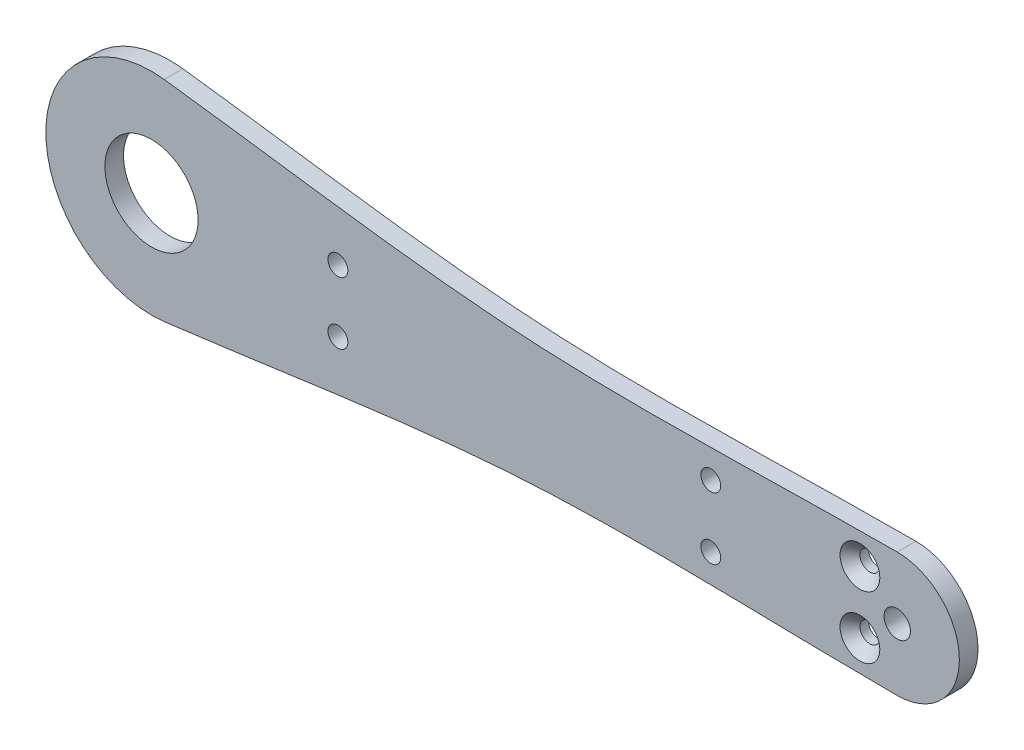
SolidWorks part; units mm, degrees
ref_plane "Front Plane" through (0, 0, 0) normal (0, 0, 1) x (1, 0, 0)
ref_plane "Top Plane" through (0, 0, 0) normal (0, 1, 0) x (1, 0, 0)
ref_plane "Right Plane" through (0, 0, 0) normal (1, 0, 0) x (0, 0, -1)
sketch "Sketch1" plane through (0, 0, 0) normal (0, 0, 1) x (1, 0, 0)
  line L0 (-103.1351, 0) -> (103.1351, 0) construction
  line L3 (0, 10) -> (0, -10) construction
  circle A2 centre (-60, 0) radius 7.5
  circle A3 centre (60, 0) radius 2.125
  arc A4 (-57.9568, 16.8768) -> (-57.9568, -16.8768) centre (-60, 0) ccw
  arc A5 (60, -10) -> (60, 10) centre (60, 0) ccw
  circle A6 centre (-30, 5) radius 1.6
  circle A7 centre (30, 5) radius 1.6
  circle A8 centre (30, -5) radius 1.6
  circle A9 centre (-30, -5) radius 1.6
  spline S0 degree 3 poles (60, 10) (39.9383, 10) (0.416, 7.6936) (-38.5985, 14.4869) (-57.9568, 16.8768) knots 0 0 0 0 0.506914 1 1 1 1
  spline S1 degree 3 poles (60, -10) (39.9383, -10) (0.416, -7.6936) (-38.5985, -14.4869) (-57.9568, -16.8768) knots 0 0 0 0 0.506914 1 1 1 1
  point P7 (0, 0)
  dimension "D3" = 15
  dimension "D1" = 4.25
  dimension "D2" = 34
  dimension "D4" = 20
  dimension "D10" = 3.2
  dimension "D5" = 120
  dimension "D6" = 20
  dimension "D7" = 60
  dimension "D8" = 30
  dimension "D9" = 5
  dimension "D14" = 30
  dimension "D15" = 5
  dimension "D12" = 2
  dimension "D13" = 2
extrude "Boss-Extrude1" add sketch "Sketch1" along normal blind 3
sketch "Sketch2" plane through (0, 0, 3) normal (0, 0, 1) x (1, 0, 0)
  line L0 (60, 0) -> (73.8031, 0) construction
  circle A0 centre (60, 0) radius 2.125 construction
  circle A1 centre (60, 0) radius 2.125 construction
  circle A4 centre (54, 5) radius 1.6
  circle A5 centre (54, -5) radius 1.6
  dimension "D3" = 3.2
  dimension "D1" = 6
  dimension "D2" = 5
extrude "Cut-Extrude1" cut sketch "Sketch2" against normal through all
chamfer "Chamfer1" distance 1.6 angle 45 2 edges at (52.4, -5, 3) (55.6, 5, 3)
equation "\"L1\"= 120mm'Upper arm"
equation "\"L3\"= 75mm'Wrist→TCP"
equation "\"h0\"= 75mm'Shoulder height"
equation "\"t_link\"= 3mm'Link plate thickness"
equation "\"t_bracket\"= 4mm'Bracket thickness"
equation "\"d_pin\"= 4mm'Pin diameter (M4)"
equation "\"c_fit\"= 0.2mm'Nominal clearance - measured PLA 2026-10-01"
equation "\"L2\"= 120mm'Forearm"
equation "\"c_fit_pivot\"= \"c_fit\" + 0.05mm'Gripper pivot clearance - chosen 0.25 mm 2026-10-01"
equation "\"d_pin_gripper\"= 3mm'Gripper pivot diameter"
equation "\"w_link\"= 20mm'Link plate depth (bending direction)"
equation "\"w_gap\"= 20mm'Twin-plate gap - provisional, set by elbow servo mount"
equation "\"D1@Boss-Extrude1\"=\"t_link\""
equation "\"d_boss\"= 13mm'MG996R output boss dia - from downloaded model, verify with calipers"
equation "\"c_boss\"= 1mm'Radial clearance around servo boss"
equation "\"d_servo_hole\"= \"d_boss\" + 2 * \"c_boss\"'Plate clearance hole for servo boss (15 mm)"
equation "\"t_rim\"= 9.5mm'Min material around servo hole (M3 hole + 3 mm webs each side)"
equation "\"w_link_end\"= \"d_servo_hole\" + 2 * \"t_rim\"'Link plate end width at servo end (34 mm)"
equation "\"d_hole_m3\"= \"d_pin_gripper\" + \"c_fit\"'M3 bolt clearance hole (spacer and adapter bolts)"
equation "\"d_hole_pivot\"= \"d_pin\" + \"c_fit_pivot\"'M4 pivot hole where the pin rotates (4.25 mm)"
equation "\"D3@Sketch1\"=\"d_servo_hole\""
equation "\"D1@Sketch1\"=\"d_pin\"+\"c_fit_pivot\""
equation "\"D2@Sketch1\"=\"w_link_end\""
equation "\"D4@Sketch1\"=\"w_link\""
equation "\"D5@Sketch1\"=\"L1\""
equation "\"D6@Sketch1\"=\"w_link\""
equation "\"D10@Sketch1\"=\"d_hole_m3\""
equation "\"d_horn\"= 20mm'Horn disc diameter (circular horn) - from MG996R model"
equation "\"t_horn\"= 2.3mm'Horn disc thickness"
equation "\"g_horn\"= 2.2mm'Gap from horn disc to plate 2 inner face - from MockShoulder"
equation "\"d_horn_pocket\"= \"d_horn\" + \"c_fit\"'Adapter pocket for horn disc (20.2 mm)"
equation "\"h_horn_pocket\"= \"g_horn\" + \"t_horn\"'Pocket depth from adapter plate-2 face (4.5 mm)"
equation "\"d_horn_screw_cb\"= 8.5mm'Recess for horn centre-screw head (head is 7.5 mm)"
equation "\"h_horn_screw_cb\"= 2.6mm'Recess depth (head is 2.35 mm tall)"
equation "\"d_adapter\"= 26mm'Horn adapter outer diameter"
equation "\"h_adapter\"= \"w_gap\"'Adapter length, fills the plate gap"
equation "\"t_adapter_floor\"= 2mm'Floor under horn disc that the horn screws pass through"
equation "\"d_horn_screw_hole\"= 2.2mm'Clearance for M2 self-tapper through the floor"
equation "\"r_horn_screw\"= 7mm'Horn screw hole radius (14 mm square pattern)"
equation "\"d_access\"= 4mm'Access bore for the M2 screws from the plate-1 side"
equation "\"d_insert_m3\"= 4.2mm'Hole for M3 heat-set insert - check the insert maker spec"
equation "\"h_insert_m3\"= 6mm'Insert hole depth"
equation "\"x_adapter_bolt\"= 6mm'Adapter bolt offset from pin, along the arm toward its middle"
equation "\"y_adapter_bolt\"= 5mm'Adapter bolt offset from pin, across the arm (+/-)"
equation "\"d_csk_m3\"= 6.4mm'Countersink diameter in plate 1 for M3 flat head (90 deg)"
equation "\"h_pin_bore\"= 10mm'M4 pin engagement depth in the adapter"
equation "\"D1@Sketch2\"=\"x_adapter_bolt\""
equation "\"D2@Sketch2\"=\"y_adapter_bolt\""
equation "\"D3@Sketch2\"=\"d_hole_m3\""
equation "\"D1@Chamfer1\"=(\"d_csk_m3\" - \"d_hole_m3\") / 2"
